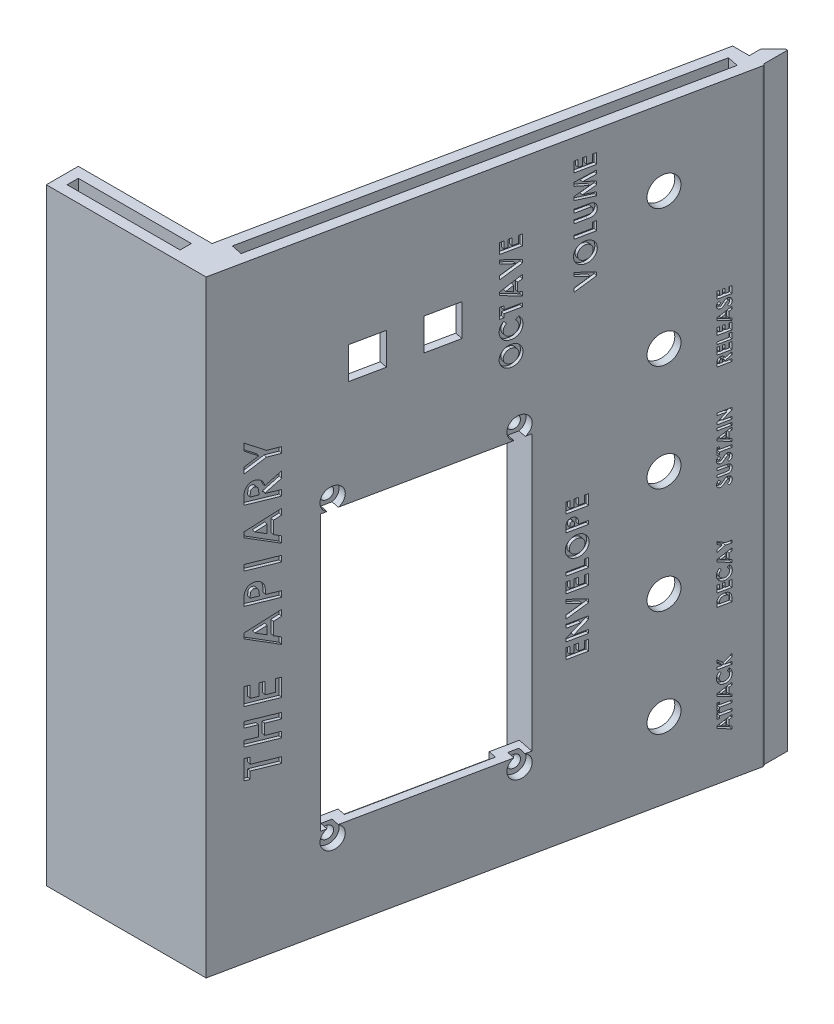
SolidWorks part; units mm, degrees
ref_plane "Front Plane" through (0, 0, 0) normal (1, 0, 0) x (0, 1, 0)
ref_plane "Top Plane" through (0, 0, 0) normal (0, 0, 1) x (0, 1, 0)
ref_plane "Right Plane" through (0, 0, 0) normal (0, 1, 0) x (-1, 0, 0)
sketch "Sketch1" plane through (0, 0, 0) normal (0, 1, 0) x (-1, 0, 0)
  line L0 (-10.3119, 2.5706) -> (19.6881, 147.5706)
  line L1 (-10.3119, -4.9294) -> (-5.3119, -4.9294)
  line L2 (-10.3119, -4.9294) -> (-10.3119, 2.5706)
  line L3 (-10.3119, 2.5706) -> (-5.3119, 2.5706)
  line L4 (-5.3119, -4.9294) -> (-5.3119, 2.5706)
  line L13 (-10.3119, 2.5706) -> (19.6881, 147.5706)
  line L14 (-10.3119, 2.5706) -> (-0.5193, 0.5446)
  line L15 (-10.3119, 2.5706) -> (69.6881, 2.5706) construction
  line L16 (-10.3119, 2.5706) -> (-10.3119, 137.5706) construction
  line L17 (-10.3119, 137.5706) -> (69.6881, 137.5706) construction
  line L18 (69.6881, 2.5706) -> (69.6881, 137.5706) construction
  line L19 (69.6881, 137.5706) -> (19.6881, 137.5706)
  line L20 (69.6881, 137.5706) -> (69.6881, 147.5706)
  line L21 (69.6881, 147.5706) -> (19.6881, 147.5706)
  line L22 (19.6881, 137.5706) -> (19.6881, 147.5706)
  line L23 (19.6881, 147.5706) -> (29.4807, 145.5446)
  line L24 (-0.5193, 0.5446) -> (29.4807, 145.5446)
  line L25 (-5.3119, 2.5706) -> (-0.1001, 2.5706)
  dimension "D3" = 135
  dimension "D4" = 80
  dimension "D5" = 10
  dimension "D7" = 10
  dimension "D6" = 50
extrude "Boss-Extrude1" add sketch "Sketch1" along normal blind 190 contours L14 L2 L1 L4 | L3 L14 L4 | L3 L25 L24 L19 L22 L0 | L24 L19 L20 L21 L23 | L19 L24 L23 L22 region at (7.8736, 0, -1.4316) region at (-8.8358, 0, 70.5982) region at (6.9786, 0, 2.2258) region at (-24.0345, 0, 142.2329) region at (-48.706, 0, 142.6363)
sketch "Sketch3" plane through (0, 190, 0) normal (0, 1, 0) x (-1, 0, 0)
  line L1 (69.6881, 137.5706) -> (57.1881, 137.5706) construction
  line L2 (69.6881, 137.5706) -> (69.6881, 127.0706) construction
  line L3 (69.6881, 127.0706) -> (57.1881, 127.0706) construction
  line L4 (57.1881, 137.5706) -> (57.1881, 127.0706) construction
  line L14 (57.1881, 137.5706) -> (52.1881, 137.5706)
  line L15 (57.1881, 137.5706) -> (57.1881, 127.0706)
  line L16 (57.1881, 127.0706) -> (52.1881, 127.0706)
  line L17 (52.1881, 137.5706) -> (52.1881, 127.0706)
  line M9 (27.8309, 137.5706) -> (69.6881, 137.5706)
  dimension "D1" = 12.5
  dimension "D2" = 10.5
extrude "Boss-Extrude4" add sketch "Sketch3" against normal up to surface (190 mm away) contours L3 L4 M9 region at (-54.6881, 190, 132.3206) up to face at (-17.2831, 0, 63.1262)
sketch "Sketch6" plane through (0, 190, 0) normal (0, 1, 0) x (-1, 0, 0)
  line L0 (27.8309, 137.5706) -> (-0.1001, 2.5706)
  line L1 (27.8309, 137.5706) -> (69.6881, 137.5706)
  line L2 (27.8309, 137.5706) -> (27.8309, 147.5706)
  line L3 (27.8309, 147.5706) -> (69.6881, 147.5706)
  line L4 (69.6881, 137.5706) -> (69.6881, 147.5706)
  line L5 (27.8309, 137.5706) -> (18.0383, 139.5967)
  line L6 (-0.1001, 2.5706) -> (-9.8927, 4.5967)
  line L7 (18.0383, 139.5967) -> (-9.8927, 4.5967)
  line L8 (-10.3119, 2.5706) -> (19.6881, 147.5706) construction
  line L9 (23.9899, 135.0465) -> (-2.6242, 6.4117)
  line L10 (-2.6242, 6.4117) -> (-6.0517, 7.1208)
  line L11 (20.5624, 135.7556) -> (-6.0517, 7.1208)
  line L12 (23.9899, 135.0465) -> (20.5624, 135.7556)
  line L13 (31.0809, 140.8206) -> (31.0809, 144.3206)
  line L14 (31.0809, 144.3206) -> (66.4381, 144.3206)
  line L15 (66.4381, 140.8206) -> (66.4381, 144.3206)
  line L16 (31.0809, 140.8206) -> (66.4381, 140.8206)
  line L18 (20.5624, 135.7556) -> (23.0069, 147.5706)
  line L19 (69.6881, 147.5706) -> (19.6881, 147.5706) construction
  line L20 (23.9899, 135.0465) -> (26.5811, 147.5706)
  line L21 (26.5811, 147.5706) -> (23.0069, 147.5706)
  line L22 (31.0809, 144.3206) -> (22.3345, 144.3206)
  line L23 (22.3345, 144.3206) -> (21.6104, 140.8206)
  line L24 (21.6104, 140.8206) -> (31.0809, 140.8206)
  dimension "D1" = 3.25
extrude "Cut-Extrude1" cut sketch "Sketch6" against normal blind 10 contours L9 L12 L11 L10 | L13 L16 L15 L14 region at (-48.7595, 190, 142.5706) region at (-8.9691, 190, 71.0836)
ref_plane "Plane2" through (0, 95, 0) normal (0, 1, 0) x (1, 0, 0)
mirror "Mirror1" about plane through (0, 95, 0) normal (0, 1, 0) of "Cut-Extrude1"
sketch "Sketch5" plane through (0.606, 0, 0.1254) normal (-0.9793, 0, -0.2026) x (0, -1, 0)
  line L1 (0, 140.3562) -> (-120, 140.3562)
  line L2 (0, 140.3562) -> (0, 2.497)
  line L3 (0, 2.497) -> (-120, 2.497)
  line L4 (-120, 140.3562) -> (-120, 2.497) construction
  line L5 (-190, 2.497) -> (0, 2.497) construction
  line L6 (-120.25, 62.247) -> (-120.25, 118.247)
  line L7 (-120, 2.497) -> (-22, 2.497) construction
  line L8 (-120, 2.497) -> (-120, 62.497) construction
  line L9 (-120, 62.497) -> (-22, 62.497) construction
  line L10 (-22, 2.497) -> (-22, 62.497) construction
  line L11 (-120, 62.497) -> (-22, 62.497)
  line L12 (-120, 62.497) -> (-120, 117.997)
  line L13 (-120, 117.997) -> (-22, 117.997)
  line L14 (-22, 62.497) -> (-22, 117.997)
  line L15 (-120.25, 118.247) -> (-21.75, 118.247)
  line L16 (-21.75, 62.247) -> (-21.75, 118.247)
  line L17 (-120.25, 62.247) -> (-21.75, 62.247)
  dimension "D1" = 137.8591
  dimension "D2" = 120
  dimension "D3" = 60
  dimension "D4" = 98
  dimension "D5" = 55.5
  dimension "D6" = 0.25
extrude "Cut-Extrude2" cut sketch "Sketch5" against normal blind 5 contours L11 L14 L13 L12 | L6 L17 L16 L15 L14 L11 L12 L13 | L6 L15 L16 L17 region at (-17.6785, 120.1367, 88.5007) region at (-17.6785, 71, 88.5007)
sketch "Sketch7" plane through (5.5023, 0, 1.1384) normal (-0.9793, 0, -0.2026) x (0, -1, 0)
  line L1 (-120.25, 118.247) -> (-117, 118.247)
  line L2 (-120.25, 118.247) -> (-120.25, 114.997)
  line L3 (-120.25, 114.997) -> (-117, 114.997)
  line L4 (-117, 118.247) -> (-117, 114.997)
  circle A0 centre (-117, 114.997) radius 1.9
  dimension "D1" = 3.25
  dimension "D3" = 3.8
  dimension "D2" = 3.25
extrude "Cut-Extrude3" cut sketch "Sketch7" against normal up to next contours A0
pattern_linear "LPattern1" count 2 spacing 92 along (0, -1, 0) count 2 spacing 49.5 along (0.2026, 0, -0.9793) of "Cut-Extrude3"
sketch "Sketch9" plane through (5.5023, 0, 1.1384) normal (-0.9793, 0, -0.2026) x (0, -1, 0)
  line L0 (-120.25, 62.247) -> (-21.75, 62.247) construction
  line L1 (-120.25, 118.247) -> (-114, 118.247) construction
  line L2 (-120.25, 118.247) -> (-120.25, 62.247) construction
  line L3 (-120.25, 62.247) -> (-114, 62.247) construction
  line L4 (-114, 118.247) -> (-114, 62.247) construction
  line L6 (-21.75, 118.247) -> (-28, 118.247) construction
  line L7 (-21.75, 118.247) -> (-21.75, 62.247) construction
  line L8 (-21.75, 62.247) -> (-28, 62.247) construction
  line L9 (-28, 118.247) -> (-28, 62.247) construction
  line L10 (-114, 118.247) -> (-28, 118.247)
  line L11 (-114, 118.247) -> (-114, 62.247)
  line L12 (-114, 62.247) -> (-28, 62.247)
  line L13 (-28, 118.247) -> (-28, 62.247)
  dimension "D1" = 6.25
  dimension "D2" = 6.25
extrude "Cut-Extrude5" cut sketch "Sketch9" against normal up to next
sketch "Sketch8" plane through (5.5023, 0, 1.1384) normal (-0.9793, 0, -0.2026) x (0, -1, 0)
  line L0 (-21.75, 62.247) -> (-21.75, 118.247) construction
  line L1 (-21.75, 62.247) -> (-28, 62.247) construction
  line L2 (-21.75, 62.247) -> (-21.75, 70.247) construction
  line L3 (-21.75, 70.247) -> (-28, 70.247) construction
  line L4 (-28, 62.247) -> (-28, 70.247) construction
  line L5 (-28, 70.247) -> (-21.75, 70.247)
  line L6 (-28, 70.247) -> (-28, 110.247)
  line L7 (-28, 110.247) -> (-21.75, 110.247)
  line L8 (-21.75, 70.247) -> (-21.75, 110.247)
  line L9 (-120.25, 118.247) -> (-21.75, 118.247) construction
  line L10 (-21.75, 118.247) -> (-28, 118.247) construction
  line L11 (-21.75, 118.247) -> (-21.75, 110.247) construction
  line L12 (-21.75, 110.247) -> (-28, 110.247) construction
  line L13 (-28, 118.247) -> (-28, 110.247) construction
  line L14 (-120.25, 118.247) -> (-114, 118.247) construction
  line L15 (-28, 62.247) -> (-28, 118.247) construction
  dimension "D1" = 8
  dimension "D2" = 8
extrude "Cut-Extrude4" cut sketch "Sketch8" against normal blind 2.5 contours L7 L6 L3 region at (-12.7822, 24.875, 89.5137)
sketch "Sketch10" plane through (10.3986, 0, 2.1514) normal (0.9793, 0, 0.2026) x (0, 1, 0)
  circle A0 centre (25, 114.997) radius 3.35
  dimension "D1" = 6.7
extrude "Cut-Extrude6" cut sketch "Sketch10" against normal blind 2.5
pattern_linear "LPattern2" count 2 spacing 92 along (0, 1, 0) count 2 spacing 49.5 along (0.2026, 0, -0.9793) of "Cut-Extrude6"
sketch "Sketch11" plane through (10.3986, 0, 2.1514) normal (0.9793, 0, 0.2026) x (0, 1, 0)
  line L1 (0, 0.4281) -> (28, 0.4281) construction
  line L2 (0, 0.4281) -> (0, 62.247) construction
  line L3 (0, 62.247) -> (28, 62.247) construction
  line L4 (28, 0.4281) -> (28, 62.247) construction
  line L6 (0, 27.247) -> (23.75, 27.247) construction
  line L7 (0, 27.247) -> (0, 62.247) construction
  line L8 (0, 62.247) -> (23.75, 62.247) construction
  line L9 (23.75, 27.247) -> (23.75, 62.247) construction
  line L10 (190, 0.4281) -> (0, 0.4281) construction
  line L11 (0, 0.4281) -> (0, 148.499) construction
  circle A0 centre (23.75, 27.247) radius 4.5
  dimension "D3" = 9
  dimension "D2" = 23.75
  dimension "D1" = 35
extrude "Cut-Extrude7" cut sketch "Sketch11" against normal up to next
mirror "Mirror2" about plane through (0, 95, 0) normal (0, 1, 0) of "Cut-Extrude7"
pattern_linear "LPattern3" count 4 spacing 33.25 along (0, 1, 0) of "Cut-Extrude7"
sketch "Sketch15" plane through (10.3986, 0, 2.1514) normal (0.9793, 0, 0.2026) x (0, 1, 0)
  line L0 (190, 0.4281) -> (190, 148.499) construction
  line L1 (190, 118.247) -> (114, 118.247) construction
  line L2 (190, 118.247) -> (190, 62.547) construction
  line L3 (190, 62.547) -> (114, 62.547) construction
  line L4 (114, 118.247) -> (114, 62.547) construction
  line L5 (114, 118.247) -> (114, 116.4878) construction
  line L6 (152, 118.247) -> (152, 105.747) construction
  line L7 (152, 105.747) -> (152, 85.747) construction
  line L8 (147, 100.747) -> (157, 100.747)
  line L9 (147, 100.747) -> (147, 110.747)
  line L10 (147, 110.747) -> (157, 110.747)
  line L11 (157, 100.747) -> (157, 110.747)
  line L12 (147, 100.747) -> (157, 110.747) construction
  line L13 (147, 110.747) -> (157, 100.747) construction
  line L14 (147, 80.747) -> (157, 80.747)
  line L15 (147, 80.747) -> (147, 90.747)
  line L16 (147, 90.747) -> (157, 90.747)
  line L17 (157, 80.747) -> (157, 90.747)
  line L18 (147, 80.747) -> (157, 90.747) construction
  line L19 (147, 90.747) -> (157, 80.747) construction
  line L20 (114, 118.247) -> (190, 118.247) construction
  line L21 (114, 118.247) -> (114, 90.397) construction
  line L22 (114, 90.397) -> (190, 90.397) construction
  line L23 (190, 118.247) -> (190, 90.397) construction
  line L24 (152, 85.747) -> (152, 62.547) construction
  point P8 (152, 105.747)
  point P17 (152, 85.747)
  dimension "D1" = 10
  dimension "D2" = 10
  dimension "D3" = 10
  dimension "D4" = 10
  dimension "D5" = 27.85
  dimension "D6" = 55.7
  dimension "D7" = 12.5
  dimension "D8" = 20
  dimension "D9" = 23.2
extrude "Cut-Extrude9" cut sketch "Sketch15" against normal up to next contours L11 L10 L9 L8 | L17 L16 L15 L14
sketch "Sketch13" plane through (10.3986, 0, 2.1514) normal (0.9793, 0, 0.2026) x (0, 1, 0)
  line L0 (28, 62.247) -> (114, 62.247) construction
  line L1 (28, 62.247) -> (28, 47.247) construction
  line L2 (114, 62.247) -> (114, 47.247) construction
  line L3 (28, 47.247) -> (114, 47.247) construction
  line L8 (11.25, 45.2239) -> (11.25, 9.2701) construction
  line L13 (190, 0.4281) -> (190, 148.499) construction
  line L14 (114, 54.747) -> (190, 54.747) construction
  line L16 (114, 62.247) -> (190, 62.247) construction
  line L17 (190, 54.747) -> (190, 62.247) construction
  line L19 (0, 148.499) -> (190, 148.499) construction
  line L20 (0, 148.499) -> (0, 128.499) construction
  line L21 (0, 128.499) -> (190, 128.499) construction
  line L22 (190, 148.499) -> (190, 128.499) construction
  line L23 (0, 0.4281) -> (190, 0.4281) construction
  line L24 (0, 0.4281) -> (0, 5.4281) construction
  line L25 (0, 5.4281) -> (190, 5.4281) construction
  line L26 (190, 0.4281) -> (190, 5.4281) construction
  line L54 (11.25, 45.2239) -> (36.25, 45.2239) construction
  line L55 (11.25, 9.2701) -> (36.25, 9.2701) construction
  line L56 (36.25, 45.2239) -> (36.25, 9.2701) construction
  line L57 (11.25, 45.2239) -> (36.25, 9.2701) construction
  line L58 (11.25, 9.2701) -> (36.25, 45.2239) construction
  line L59 (44.5, 45.2239) -> (44.5, 9.2701) construction
  line L60 (44.5, 45.2239) -> (69.5, 45.2239) construction
  line L61 (44.5, 9.2701) -> (69.5, 9.2701) construction
  line L62 (69.5, 45.2239) -> (69.5, 9.2701) construction
  line L63 (44.5, 45.2239) -> (69.5, 9.2701) construction
  line L64 (44.5, 9.2701) -> (69.5, 45.2239) construction
  line L65 (77.75, 45.2239) -> (77.75, 9.2701) construction
  line L66 (77.75, 45.2239) -> (102.75, 45.2239) construction
  line L67 (77.75, 9.2701) -> (102.75, 9.2701) construction
  line L68 (102.75, 45.2239) -> (102.75, 9.2701) construction
  line L69 (77.75, 45.2239) -> (102.75, 9.2701) construction
  line L70 (77.75, 9.2701) -> (102.75, 45.2239) construction
  line L71 (111, 45.2239) -> (111, 9.2701) construction
  line L72 (111, 45.2239) -> (136, 45.2239) construction
  line L73 (111, 9.2701) -> (136, 9.2701) construction
  line L74 (136, 45.2239) -> (136, 9.2701) construction
  line L75 (111, 45.2239) -> (136, 9.2701) construction
  line L76 (111, 9.2701) -> (136, 45.2239) construction
  line L77 (146.25, 49.066) -> (146.25, 5.4281) construction
  line L78 (146.25, 49.066) -> (186.25, 49.066) construction
  line L79 (146.25, 5.4281) -> (186.25, 5.4281) construction
  line L80 (186.25, 49.066) -> (186.25, 5.4281) construction
  line L81 (146.25, 49.066) -> (186.25, 5.4281) construction
  line L82 (146.25, 5.4281) -> (186.25, 49.066) construction
  line L83 (146.25, 2.9281) -> (186.25, 2.9281) construction
  line L84 (146.25, 5.4281) -> (186.25, 5.4281) construction
  line L85 (146.25, 5.4281) -> (146.25, 0.4281) construction
  line L86 (146.25, 0.4281) -> (186.25, 0.4281) construction
  line L87 (186.25, 5.4281) -> (186.25, 0.4281) construction
  line L89 (146.25, 49.066) -> (186.25, 49.066) construction
  line L90 (146.25, 49.066) -> (146.25, 45.066) construction
  line L91 (146.25, 45.066) -> (186.25, 45.066) construction
  line L92 (186.25, 49.066) -> (186.25, 45.066) construction
  line L93 (114, 62.247) -> (190, 62.247) construction
  line L94 (114, 62.247) -> (114, 64.747) construction
  line L95 (114, 64.747) -> (190, 64.747) construction
  line L96 (190, 62.247) -> (190, 64.747) construction
  circle A0 centre (23.75, 27.247) radius 4.5 construction
  text T0 "<b>ENVELOPE</b>" font "Century Gothic" height 6
  text T1 "<b>OCTAVE</b>" font "Century Gothic" height 6
  text T2 "<b>ATTACK</b>" font "Century Gothic" height 4
  text T3 "<b>DECAY</b>" font "Century Gothic" height 4
  text T4 "<b>SUSTAIN</b>" font "Century Gothic" height 4
  text T5 "<b>RELEASE</b>" font "Century Gothic" height 4
  text T6 "<b>THE APIARY</b>" font "Century Gothic" height 10
  text T7 "<b>VOLUME</b>" font "Century Gothic" height 6
  point P24 (166.25, 27.247)
  point P25 (23.75, 27.247)
  point P26 (57, 27.247)
  point P27 (123.5, 27.247)
  point P30 (90.25, 27.247)
  dimension "D10" = 4
  dimension "D1" = 15
  dimension "D2" = 20
  dimension "D3" = 5
  dimension "D4" = 25
  dimension "D5" = 25
  dimension "D6" = 25
  dimension "D7" = 25
  dimension "D8" = 40
  dimension "D9" = 5
  dimension "D11" = 2.5
extrude "Cut-Extrude8" cut sketch "Sketch13" against normal blind 1
sketch "Sketch17" plane through (-57.1881, 0, 0) normal (-1, 0, 0) x (0, -1, 0)
  line L0 (0, 137.5706) -> (-190, 137.5706) construction
  line L1 (0, 137.5706) -> (-23.5, 137.5706) construction
  line L2 (0, 137.5706) -> (0, 130.5706) construction
  line L3 (0, 130.5706) -> (-23.5, 130.5706) construction
  line L4 (-23.5, 137.5706) -> (-23.5, 130.5706) construction
  line L5 (-190, 137.5706) -> (0, 137.5706) construction
  line L6 (0, 127.0706) -> (0, 137.5706) construction
  line L7 (-190, 2.5706) -> (-190, 137.5706) construction
  line L8 (-190, 137.5706) -> (-167.5, 137.5706) construction
  line L9 (-190, 137.5706) -> (-190, 130.5706) construction
  line L10 (-190, 130.5706) -> (-167.5, 130.5706) construction
  line L11 (-167.5, 137.5706) -> (-167.5, 130.5706) construction
  line L12 (-167.5, 130.5706) -> (-144.5, 130.5706) construction
  line L13 (-167.5, 130.5706) -> (-167.5, 137.5706) construction
  line L14 (-167.5, 137.5706) -> (-144.5, 137.5706) construction
  line L15 (-144.5, 130.5706) -> (-144.5, 137.5706) construction
  circle A0 centre (-23.5, 130.5706) radius 1.9
  circle A1 centre (-114, 130.5706) radius 1.9
  circle A2 centre (-167.5, 130.5706) radius 1.9
  circle A3 centre (-144.5, 130.5706) radius 1.9
  dimension "D3" = 3.8
  dimension "D10" = 3.8
  dimension "D1" = 23.5
  dimension "D2" = 7
  dimension "D5" = 90.5
  dimension "D7" = 23
  dimension "D8" = 76
  dimension "D9" = 22.5
  dimension "D4" = 2
  dimension "D11" = 2
extrude "Cut-Extrude10" cut sketch "Sketch17" against normal up to next
sketch "Sketch18" plane through (-57.1881, 0, 0) normal (-1, 0, 0) x (0, -1, 0)
  line L0 (0, 127.0706) -> (-190, 127.0706) construction
  line L1 (0, 137.5706) -> (-18.5, 137.5706)
  line L2 (0, 137.5706) -> (0, 127.0706)
  line L3 (0, 127.0706) -> (-18.5, 127.0706)
  line L4 (-18.5, 137.5706) -> (-18.5, 127.0706)
  line L5 (0, 137.5706) -> (-190, 137.5706) construction
  line L6 (-18.5, 127.0706) -> (-28.5, 127.0706) construction
  line L7 (-18.5, 127.0706) -> (-18.5, 137.5706) construction
  line L8 (-18.5, 137.5706) -> (-28.5, 137.5706) construction
  line L9 (-28.5, 127.0706) -> (-28.5, 137.5706) construction
  line L10 (-190, 137.5706) -> (0, 137.5706) construction
  line L11 (-28.5, 137.5706) -> (-109, 137.5706)
  line L12 (-28.5, 137.5706) -> (-28.5, 127.0706)
  line L13 (-28.5, 127.0706) -> (-109, 127.0706)
  line L14 (-109, 137.5706) -> (-109, 127.0706)
  line L15 (-109, 127.0706) -> (-119, 127.0706) construction
  line L16 (-109, 127.0706) -> (-109, 137.5706) construction
  line L17 (-109, 137.5706) -> (-119, 137.5706) construction
  line L18 (-119, 127.0706) -> (-119, 137.5706) construction
  line L24 (-119, 137.5706) -> (-139.5, 137.5706)
  line L25 (-119, 137.5706) -> (-119, 127.0706)
  line L26 (-119, 127.0706) -> (-139.5, 127.0706)
  line L27 (-139.5, 137.5706) -> (-139.5, 127.0706)
  line L28 (-139.5, 127.0706) -> (-149.5, 127.0706) construction
  line L29 (-139.5, 127.0706) -> (-139.5, 137.5706) construction
  line L30 (-139.5, 137.5706) -> (-149.5, 137.5706) construction
  line L31 (-149.5, 127.0706) -> (-149.5, 137.5706) construction
  line L32 (-149.5, 137.5706) -> (-162.5, 137.5706)
  line L33 (-149.5, 137.5706) -> (-149.5, 127.0706)
  line L34 (-149.5, 127.0706) -> (-162.5, 127.0706)
  line L35 (-162.5, 137.5706) -> (-162.5, 127.0706)
  line L36 (-162.5, 127.0706) -> (-172.5, 127.0706) construction
  line L37 (-162.5, 127.0706) -> (-162.5, 137.5706) construction
  line L38 (-162.5, 137.5706) -> (-172.5, 137.5706) construction
  line L39 (-172.5, 127.0706) -> (-172.5, 137.5706) construction
  line L40 (-172.5, 137.5706) -> (-190, 137.5706)
  line L41 (-172.5, 137.5706) -> (-172.5, 127.0706)
  line L42 (-172.5, 127.0706) -> (-190, 127.0706)
  line L43 (-190, 137.5706) -> (-190, 127.0706)
  line M17 (-190, 127.0706) -> (0, 127.0706)
  line M18 (0, 127.0706) -> (0, 137.5706)
  line M19 (0, 137.5706) -> (-190, 137.5706)
  line M20 (-190, 137.5706) -> (-190, 127.0706)
  dimension "D5" = 20.5
  dimension "D1" = 18.5
  dimension "D2" = 10
  dimension "D3" = 80.5
  dimension "D4" = 10
  dimension "D6" = 10
  dimension "D7" = 13
  dimension "D8" = 10
  dimension "D9" = 17.5
extrude "Cut-Extrude11" cut sketch "Sketch18" against normal up to next contours L14 L12 M19 M17 | L4 M19 M17 M18 | L35 L33 M19 M17 | L41 M19 M20 M17 region at (-57.1881, 9.25, 132.3206) region at (-57.1881, 68.75, 132.3206) region at (-57.1881, 156, 132.3206) region at (-57.1881, 181.25, 132.3206)
sketch "Sketch19" plane through (0.606, 0, 0.1254) normal (-0.9793, 0, -0.2026) x (0, -1, 0)
  line L0 (0, 2.497) -> (0, 140.3562) construction
  line L1 (-190, 2.497) -> (-123.5, 2.497) construction
  line L2 (-190, 2.497) -> (-190, 27.247) construction
  line L3 (-190, 27.247) -> (-123.5, 27.247) construction
  line L4 (-123.5, 2.497) -> (-123.5, 27.247) construction
  line L5 (-190, 2.497) -> (0, 2.497)
  line L6 (-190, 2.497) -> (-190, 51.997)
  line L7 (-190, 51.997) -> (0, 51.997)
  line L8 (0, 2.497) -> (0, 51.997)
  line L9 (-185, 7.497) -> (-185, 46.997)
  line L10 (-185, 46.997) -> (-5, 46.997)
  line L11 (-5, 7.497) -> (-5, 46.997)
  line L12 (-185, 7.497) -> (-5, 7.497)
  line L18 (-152, 105.747) -> (-152, 85.747) construction
  line L19 (-157, 110.747) -> (-147, 110.747)
  line L20 (-157, 110.747) -> (-157, 100.747)
  line L21 (-157, 100.747) -> (-147, 100.747)
  line L22 (-147, 110.747) -> (-147, 100.747)
  line L23 (-157, 110.747) -> (-147, 100.747) construction
  line L24 (-157, 100.747) -> (-147, 110.747) construction
  line L25 (-157, 90.747) -> (-147, 90.747)
  line L26 (-157, 90.747) -> (-157, 80.747)
  line L27 (-157, 80.747) -> (-147, 80.747)
  line L28 (-147, 90.747) -> (-147, 80.747)
  line L29 (-157, 90.747) -> (-147, 80.747) construction
  line L30 (-157, 80.747) -> (-147, 90.747) construction
  line L31 (-177.5, 14.997) -> (-177.5, 39.497)
  line L32 (-167, 67.897) -> (-137, 67.897)
  line L33 (-167, 67.897) -> (-167, 123.597)
  line L34 (-167, 123.597) -> (-137, 123.597)
  line L35 (-137, 67.897) -> (-137, 123.597)
  line L36 (-167, 67.897) -> (-137, 123.597) construction
  line L37 (-167, 123.597) -> (-137, 67.897) construction
  line L38 (-177.5, 39.497) -> (-12.5, 39.497)
  line L39 (-12.5, 14.997) -> (-12.5, 39.497)
  line L40 (-177.5, 14.997) -> (-12.5, 14.997)
  line L42 (-185, 46.997) -> (-177.5, 46.997)
  line L43 (-185, 46.997) -> (-185, 7.497)
  line L44 (-185, 7.497) -> (-177.5, 7.497)
  line L45 (-177.5, 46.997) -> (-177.5, 7.497)
  line L46 (-5, 46.997) -> (-12.5, 46.997)
  line L47 (-5, 46.997) -> (-5, 7.497)
  line L48 (-5, 7.497) -> (-12.5, 7.497)
  line L49 (-12.5, 46.997) -> (-12.5, 7.497)
  point P27 (-152, 105.747)
  point P34 (-152, 85.747)
  point P39 (-152, 95.747)
  line M3 (-147, 110.747) -> (-147, 100.747)
  line M4 (-147, 100.747) -> (-157, 100.747)
  line M5 (-157, 100.747) -> (-157, 110.747)
  line M6 (-157, 110.747) -> (-147, 110.747)
  line M7 (-147, 90.747) -> (-147, 80.747)
  line M8 (-147, 80.747) -> (-157, 80.747)
  line M9 (-157, 80.747) -> (-157, 90.747)
  line M10 (-157, 90.747) -> (-147, 90.747)
  circle M11 centre (-57, 27.247) radius 4.5
  circle M12 centre (-90.25, 27.247) radius 4.5
  circle M13 centre (-123.5, 27.247) radius 4.5
  circle M14 centre (-23.75, 27.247) radius 4.5
  dimension "D1" = 24.75
  dimension "D2" = 49.5
  dimension "D5" = 30
  dimension "D6" = 7.5
extrude "Cut-Extrude12" cut sketch "Sketch19" against normal blind 7.5 contours L9 L12 L11 L10 M11 M13 M14 M12 | L32 L35 L34 L33 M10 M7 M8 M9 M6 M3 M4 M5 | L49 L10 L45 L38 | L49 L40 L45 L12 region at (-1.6727, 95, 11.1391) region at (-8.1561, 95, 42.4755) region at (-4.9144, 96.4359, 26.8073) region at (-18.7929, 152, 93.8867)
sketch "Sketch16" plane through (10.3986, 0, 2.1514) normal (0.9793, 0, 0.2026) x (0, 1, 0)
  circle A0 centre (23.75, 27.247) radius 10
extrude "Boss-Extrude5" [suppressed] add sketch "Sketch16" along normal blind 10
pattern_linear "LPattern4" [suppressed] count 4 spacing 41.1667 of bodies 117
sketch "Sketch20" plane through (0, 190, 0) normal (0, 1, 0) x (-1, 0, 0)
  line L0 (-10.3119, -4.9294) -> (-5.3119, -4.9294) construction
  line L1 (-10.3119, 2.5706) -> (-9.8119, 2.5706)
  line L2 (-10.3119, 2.5706) -> (-10.3119, -4.9294)
  line L3 (-10.3119, -4.9294) -> (-9.8119, -4.9294)
  line L4 (-9.8119, 2.5706) -> (-9.8119, -4.9294)
extrude "Cut-Extrude13" cut sketch "Sketch20" against normal up to next
chamfer "Chamfer1" distance 4 angle 45 1 edges at (5.3119, 95, -4.9294)
fillet "Fillet1" radius 0.5 1 edges at (10.3119, 95, 2.5706)
chamfer "Chamfer2" [suppressed] distance 5 distance2 5
equation "\"whitekey_cutout_length\"= 101.5"
equation "\"key_mount_recess_length\"=50"
equation "\"key_mount_recess_height\"=12.5"
equation "\"key_mount_recess_depth\"=1.5"
equation "\"wall_thickness\"=10"
equation "\"guide_brace_height\"=20"
equation "\"guide_brace_thickness\"=2"
equation "\"dowel_recess_depth\"=10"
equation "\"dowel_recess_offset\"=3.25"
equation "\"dowel_insert_tolerance\"=0.1"
equation "\"base_mount_height\"=40"
equation "\"base_rear_length\"=80"
equation "\"base_front_length\"=111.5"
equation "\"screw_hole_wall_offset\"=7.25"
equation "\"screw_hole_edge_inset\"=\"dowel_recess_depth\"/2"
equation "\"screw_hole_diameter\"=3.8"
equation "\"screw_head_hole_diameter\"=6.7"
equation "\"screw_nut_hole_side_len\"=3.5"
equation "\"screw_nut_recess_offset\"=0.35"
equation "\"screw_head_and_nut_recess_depth\"=2.5"
equation "\"screw_shaft_diameter\"=3.5"
equation "\"switch_board_width\"=30"
equation "\"switch_board_thickness\"=1.6"
equation "\"switch_board_wall_offset\"=11.5"
equation "\"heatset_insert_hole_diameter\"=4.8"
equation "\"heatset_insert_hole_depth\"=3.8"
equation "\"front_rear_panel_width\"=23.75"
equation "\"front_panel_height\"=24"
equation "\"front_rear_panel_recess_depth\"=5"
equation "\"rod_diameter\"=5"
equation "\"rod_head_diameter\"=8"
equation "\"rod_length_adj\"=0.5"
equation "\"rod_insert_length\"=2.8"
equation "\"switch_black_key_mount_height\"=8"
equation "\"switch_white_key_mount_height\"=3"
equation "\"D1@Sketch1\"=\"wall_thickness\"*0.75"
equation "\"D2@Sketch1\"=\"wall_thickness\"/2"
equation "\"D3@Sketch1\"=\"interface_panel_height\""
equation "\"D4@Sketch1\"=\"base_rear_length\""
equation "\"D5@Sketch1\"=\"wall_thickness\""
equation "\"D1@Boss-Extrude1\"=\"front_rear_panel_width\"*8"
equation "\"D1@Sketch3\"=\"wall_thickness\"*1.25"
equation "\"D2@Sketch3\"=\"screw_shaft_diameter\"*3"
equation "\"D1@Sketch6\"=\"dowel_recess_offset\""
equation "\"D7@Sketch1\"=\"wall_thickness\""
equation "\"D1@Cut-Extrude1\"=\"dowel_recess_depth\""
equation "\"D1@Cut-Extrude2\"=\"wall_thickness\"/2"
equation "\"D3@Sketch7\"=\"screw_hole_diameter\""
equation "\"D1@Cut-Extrude4\"=\"wall_thickness\"/4"
equation "\"D1@Sketch10\"=\"screw_head_hole_diameter\""
equation "\"D1@Cut-Extrude6\"=\"screw_head_and_nut_recess_depth\""
equation "\"D3@Sketch3\"=\"wall_thickness\"/2"
equation "\"D2@Sketch11\"=(\"front_rear_panel_width\"*8)*0.125"
equation "\"D3@Sketch11\"=9"
equation "\"D3@LPattern3\"=(\"front_rear_panel_width\"*8)*0.525/3"
equation "\"D3@Sketch17\"=\"screw_hole_diameter\""
equation "\"D1@Cut-Extrude12\"=\"wall_thickness\"*0.75"
equation "\"D3@LPattern4\"=(\"front_rear_panel_width\"*8)*0.65/3"
equation "\"D10@Sketch17\"=\"screw_hole_diameter\""
equation "\"whitekey_spacing\"=1.25"
equation "\"side_panel_depth\"=35"
equation "\"interface_panel_height\"=135"
equation "\"interface_panel_roof_length\"=50"
equation "\"D6@Sketch1\"=\"interface_panel_roof_length\""
equation "\"D1@Sketch20\"=\"whitekey_spacing\"*0.4"
equation "\"D2@Sketch19\"=2*\"D1@Sketch19\""
equation "\"D1@Sketch7\"=3+\"D6@Sketch5\""
equation "\"D2@Sketch7\"=\"D1@Sketch7\""
equation "\"D2@Sketch9\"=\"D1@Sketch9\""
